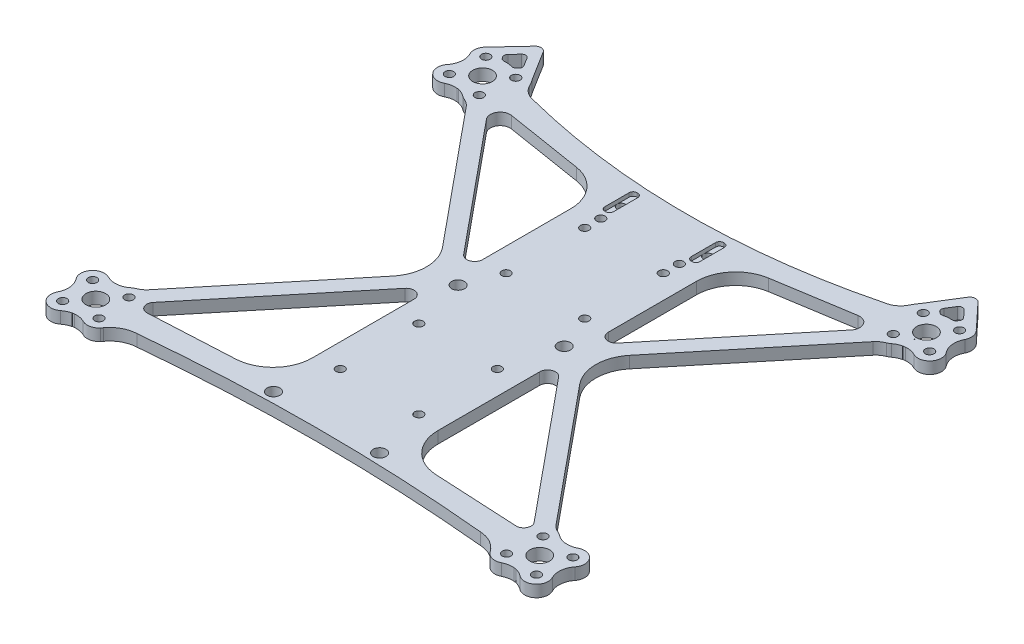
SolidWorks part; units mm, degrees
ref_plane "Front Plane" through (0, 0, 0) normal (0, 0, 1) x (1, 0, 0)
ref_plane "Top Plane" through (0, 0, 0) normal (0, 1, 0) x (1, 0, 0)
ref_plane "Right Plane" through (0, 0, 0) normal (1, 0, 0) x (0, 0, -1)
sketch "Sketch1" plane through (0, 0, 0) normal (0, 1, 0) x (1, 0, 0)
  line L0 (0, 42.225) -> (0, -42.225) construction
  line L1 (16, 42.225) -> (-16, 42.225)
  line L2 (16, 42.225) -> (16, -42.225)
  line L3 (16, -42.225) -> (-16, -42.225)
  line L4 (-16, 42.225) -> (-16, -42.225)
  line L5 (16, 42.225) -> (-16, -42.225) construction
  line L6 (16, -42.225) -> (-16, 42.225) construction
  line L17 (-16, 42.225) -> (16, 42.225)
  line L19 (-16, 42.225) -> (-16, 52.425)
  line L20 (-10, 36) -> (10, 36)
  line L21 (-10, 36) -> (-10, 16)
  line L22 (-10, 16) -> (10, 16)
  line L23 (10, 36) -> (10, 16)
  line L24 (-10, 36) -> (10, 16) construction
  line L25 (-10, 16) -> (10, 36) construction
  line L26 (-14.5, 10.775) -> (14.5, 10.775)
  line L27 (-14.5, 10.775) -> (-14.5, 41.225)
  line L28 (-14.5, 41.225) -> (14.5, 41.225)
  line L29 (14.5, 10.775) -> (14.5, 41.225)
  line L30 (-14.5, 10.775) -> (14.5, 41.225) construction
  line L31 (-14.5, 41.225) -> (14.5, 10.775) construction
  line L32 (-10, -6.225) -> (10, -6.225)
  line L33 (-10, -6.225) -> (-10, -26.225)
  line L34 (-10, -26.225) -> (10, -26.225)
  line L35 (10, -6.225) -> (10, -26.225)
  line L36 (-10, -6.225) -> (10, -26.225) construction
  line L37 (-10, -26.225) -> (10, -6.225) construction
  line L38 (-15.75, -36.225) -> (15.75, -36.225)
  line L39 (-15.75, -36.225) -> (-15.75, 3.775)
  line L40 (-15.75, 3.775) -> (15.75, 3.775)
  line L41 (15.75, -36.225) -> (15.75, 3.775)
  line L42 (-15.75, -36.225) -> (15.75, 3.775) construction
  line L43 (-15.75, 3.775) -> (15.75, -36.225) construction
  line L58 (-16, 52.425) -> (16, 52.425)
  line L63 (-12.1, 50.425) -> (-9.9, 50.425)
  line L64 (-12.1, 50.425) -> (-12.1, 42.225)
  line L65 (-12.1, 42.225) -> (-9.9, 42.225)
  line L66 (-9.9, 50.425) -> (-9.9, 42.225)
  line L67 (-12.1, 50.425) -> (-9.9, 42.225) construction
  line L68 (-12.1, 42.225) -> (-9.9, 50.425) construction
  line L78 (12.1, 50.425) -> (9.9, 50.425)
  line L79 (12.1, 50.425) -> (12.1, 42.225)
  line L80 (12.1, 42.225) -> (9.9, 42.225)
  line L81 (9.9, 50.425) -> (9.9, 42.225)
  line L82 (-14.5, 10.775) -> (-14.5, 3.775) construction
  line L83 (-14.5, 7.275) -> (16, 7.275) construction
  line L89 (-13.5, -37.225) -> (-16, -37.225) construction
  line L90 (16, 42.225) -> (16, 52.425)
  circle A3 centre (-10, 36) radius 1.1
  circle A4 centre (10, 36) radius 1.1
  circle A5 centre (10, 16) radius 1.1
  circle A6 centre (-10, 16) radius 1.1
  circle A7 centre (-10, -6.225) radius 1.1
  circle A8 centre (10, -6.225) radius 1.1
  circle A9 centre (10, -26.225) radius 1.1
  circle A10 centre (-10, -26.225) radius 1.1
  circle A37 centre (-13.5, 7.275) radius 2.5
  circle A38 centre (-13.5, 7.275) radius 1.625
  circle A39 centre (13.5, 7.275) radius 1.625
  circle A40 centre (-13.5, -39.725) radius 2.5
  circle A41 centre (-13.5, -39.725) radius 1.625
  circle A42 centre (13.5, -39.725) radius 1.625
  circle A43 centre (-11, 46.325) radius 1.1
  circle A44 centre (11, 46.325) radius 1.1
  point P0 (0, 0)
  point P8 (0, 0)
  point P16 (0, 26)
  point P26 (0, 26)
  point P31 (0, -16.225)
  point P36 (0, -16.225)
  point P61 (-11, 46.325)
  dimension "D3" = 22
  dimension "D4" = 2
  dimension "D17" = 2.2
  dimension "D22" = 5
  dimension "D23" = 3.25
  dimension "D8" = 32
  dimension "D10" = 20
  dimension "D11" = 29
  dimension "D12" = 30.45
  dimension "D13" = 40
  dimension "D14" = 31.5
  dimension "D15" = 1
  dimension "D16" = 7
  dimension "D18" = 2.2
  dimension "D20" = 8.2
  dimension "D24" = 1
extrude "Base shape" add sketch "Sketch1" along normal blind 2 contours L1 L90 L58 L19 L17 L64 L63 L66 L81 L78 L79 | A43 L64 L17 L66 | A43 L66 L63 L64 | L81 A44 L79 L78 | L79 A44 L81 L17 | L4 L3 L2 L1 | A3 | A4 | A6 | A5 | A39 | A38 | A7 | A8 | A9 | A10 | A41 | A42 region at (0, 0, -47.4493) region at (11, 0, -43.8523) region at (11, 0, -48.7977) region at (-11, 0, -43.8523) region at (-11, 0, -48.7977)
sketch "Sketch2" plane through (0, 2, 0) normal (0, -1, 0) x (1, 0, 0)
  line L0 (0, -52.425) -> (0, 42.225) construction
  line L1 (11.1, -42.225) -> (10.9, -42.225)
  line L2 (12.1, -43.225) -> (12.1, -49.425)
  line L3 (11.1, -50.425) -> (10.9, -50.425)
  line L4 (9.9, -43.225) -> (9.9, -49.425)
  line L5 (12.1, -42.225) -> (9.9, -50.425) construction
  line L6 (12.1, -50.425) -> (9.9, -42.225) construction
  line L12 (16, 42.225) -> (-16, 42.225) construction
  line L13 (-11.1, -42.225) -> (-10.9, -42.225)
  line L14 (-12.1, -43.225) -> (-12.1, -49.425)
  line L15 (-11.1, -50.425) -> (-10.9, -50.425)
  line L20 (-9.9, -43.225) -> (-9.9, -49.425)
  line L21 (-16, -52.425) -> (16, -52.425) construction
  arc A2 (12.1, -49.425) -> (11.1, -50.425) centre (11.1, -49.425) cw
  arc A3 (10.9, -50.425) -> (9.9, -49.425) centre (10.9, -49.425) cw
  arc A4 (10.9, -42.225) -> (9.9, -43.225) centre (10.9, -43.225) ccw
  arc A5 (11.1, -42.225) -> (12.1, -43.225) centre (11.1, -43.225) cw
  arc A6 (-10.9, -42.225) -> (-9.9, -43.225) centre (-10.9, -43.225) cw
  arc A7 (-11.1, -42.225) -> (-12.1, -43.225) centre (-11.1, -43.225) ccw
  arc A8 (-12.1, -49.425) -> (-11.1, -50.425) centre (-11.1, -49.425) ccw
  arc A9 (-10.9, -50.425) -> (-9.9, -49.425) centre (-10.9, -49.425) ccw
  point P0 (11, -46.325)
  dimension "D3" = 1
  dimension "D1" = 8.2
  dimension "D2" = 2.2
extrude "Cut-Extrude2" cut sketch "Sketch2" along normal blind 1
sketch "Sketch3" plane through (0, 2, 0) normal (0, 1, 0) x (1, 0, 0)
  line L0 (-11.1, 50.425) -> (-10.9, 50.425) construction
  line L1 (-9.9, 49.425) -> (-9.9, 43.225) construction
  line L2 (-10.9, 42.225) -> (-11.1, 42.225) construction
  line L3 (-12.1, 43.225) -> (-12.1, 49.425) construction
  line L4 (-11.1, 50.425) -> (-10.9, 50.425)
  line L5 (-9.9, 49.425) -> (-9.9, 43.225)
  line L6 (-10.9, 42.225) -> (-11.1, 42.225)
  line L7 (-12.1, 43.225) -> (-12.1, 49.425)
  line L8 (-16, 52.425) -> (-16, -42.225)
  line L9 (-16, 52.425) -> (-16, -42.225)
  line L10 (-16, -42.225) -> (16, -42.225)
  line L11 (16, -42.225) -> (16, 52.425)
  line L12 (10.9, 50.425) -> (11.1, 50.425) construction
  line L13 (12.1, 49.425) -> (12.1, 43.225) construction
  line L14 (11.1, 42.225) -> (10.9, 42.225) construction
  line L15 (9.9, 43.225) -> (9.9, 49.425) construction
  line L18 (-16, -42.225) -> (16, -42.225)
  line L24 (10.9, 50.425) -> (11.1, 50.425)
  line L25 (12.1, 49.425) -> (12.1, 43.225)
  line L30 (11.1, 42.225) -> (10.9, 42.225)
  line L31 (9.9, 43.225) -> (9.9, 49.425)
  line L36 (16, -42.225) -> (16, 52.425)
  line L37 (16, 52.425) -> (-16, 52.425)
  line L38 (16, 52.425) -> (-16, 52.425)
  circle A0 centre (13.5, -39.725) radius 1.625 construction
  circle A1 centre (-13.5, -39.725) radius 1.625 construction
  circle A2 centre (-13.5, 7.275) radius 1.625 construction
  circle A3 centre (-10, -6.225) radius 1.1 construction
  circle A4 centre (-10, -26.225) radius 1.1 construction
  circle A5 centre (10, -26.225) radius 1.1 construction
  circle A6 centre (10, -6.225) radius 1.1 construction
  circle A7 centre (13.5, 7.275) radius 1.625 construction
  arc A13 (-11.1, 50.425) -> (-12.1, 49.425) centre (-11.1, 49.425) ccw construction
  arc A14 (-9.9, 49.425) -> (-10.9, 50.425) centre (-10.9, 49.425) ccw construction
  circle A24 centre (-10, 16) radius 1.1 construction
  circle A25 centre (-10, 36) radius 1.1 construction
  circle A26 centre (10, 36) radius 1.1 construction
  circle A27 centre (10, 16) radius 1.1 construction
  circle A28 centre (10, 16) radius 1.1
  circle A29 centre (10, 36) radius 1.1
  circle A30 centre (-10, 36) radius 1.1
  circle A31 centre (-10, 16) radius 1.1
  circle A32 centre (13.5, 7.275) radius 1.625
  circle A33 centre (10, -6.225) radius 1.1
  circle A34 centre (10, -26.225) radius 1.1
  circle A35 centre (-10, -26.225) radius 1.1
  circle A36 centre (-10, -6.225) radius 1.1
  circle A37 centre (13.5, -39.725) radius 1.625
  circle A38 centre (-13.5, -39.725) radius 1.625
  circle A39 centre (-13.5, 7.275) radius 1.625
  arc A40 (-10.9, 42.225) -> (-9.9, 43.225) centre (-10.9, 43.225) ccw construction
  arc A41 (-12.1, 43.225) -> (-11.1, 42.225) centre (-11.1, 43.225) ccw construction
  arc A42 (-11.1, 50.425) -> (-12.1, 49.425) centre (-11.1, 49.425) ccw
  arc A43 (-9.9, 49.425) -> (-10.9, 50.425) centre (-10.9, 49.425) ccw
  arc A44 (-10.9, 42.225) -> (-9.9, 43.225) centre (-10.9, 43.225) ccw
  arc A45 (-12.1, 43.225) -> (-11.1, 42.225) centre (-11.1, 43.225) ccw
  arc A46 (10.9, 50.425) -> (9.9, 49.425) centre (10.9, 49.425) ccw construction
  arc A47 (12.1, 49.425) -> (11.1, 50.425) centre (11.1, 49.425) ccw construction
  arc A48 (11.1, 42.225) -> (12.1, 43.225) centre (11.1, 43.225) ccw construction
  arc A49 (9.9, 43.225) -> (10.9, 42.225) centre (10.9, 43.225) ccw construction
  arc A50 (10.9, 50.425) -> (9.9, 49.425) centre (10.9, 49.425) ccw
  arc A51 (12.1, 49.425) -> (11.1, 50.425) centre (11.1, 49.425) ccw
  arc A52 (11.1, 42.225) -> (12.1, 43.225) centre (11.1, 43.225) ccw
  arc A53 (9.9, 43.225) -> (10.9, 42.225) centre (10.9, 43.225) ccw
  dimension "D1" = 0
extrude "Thicker base" add sketch "Sketch3" along normal blind 1
sketch "Sketch8" plane through (0, 1, 0) normal (0, 1, 0) x (1, 0, 0)
  line L0 (9.9, 46.325) -> (9.9, 43.225) construction
  line L1 (10.9, 42.225) -> (11.1, 42.225) construction
  line L2 (12.1, 43.225) -> (12.1, 46.325) construction
  line L3 (12.1, 46.325) -> (12.1, 49.425) construction
  line L4 (11.1, 50.425) -> (10.9, 50.425) construction
  line L5 (9.9, 49.425) -> (9.9, 46.325) construction
  line L6 (-12.1, 46.325) -> (-12.1, 43.225) construction
  line L7 (-11.1, 42.225) -> (-10.9, 42.225) construction
  line L8 (-9.9, 43.225) -> (-9.9, 46.325) construction
  line L9 (-9.9, 46.325) -> (-9.9, 49.425) construction
  line L10 (-10.9, 50.425) -> (-11.1, 50.425) construction
  line L11 (-12.1, 49.425) -> (-12.1, 46.325) construction
  line L12 (9.9, 46.325) -> (9.9, 43.225)
  line L13 (10.9, 42.225) -> (11.1, 42.225)
  line L14 (12.1, 43.225) -> (12.1, 46.325)
  line L15 (12.1, 46.325) -> (12.1, 49.425)
  line L16 (11.1, 50.425) -> (10.9, 50.425)
  line L17 (9.9, 49.425) -> (9.9, 46.325)
  line L18 (-12.1, 46.325) -> (-12.1, 43.225)
  line L19 (-11.1, 42.225) -> (-10.9, 42.225)
  line L20 (-9.9, 43.225) -> (-9.9, 46.325)
  line L21 (-9.9, 46.325) -> (-9.9, 49.425)
  line L22 (-10.9, 50.425) -> (-11.1, 50.425)
  line L23 (-12.1, 49.425) -> (-12.1, 46.325)
  arc A0 (9.9, 46.325) -> (12.1, 46.325) centre (11, 46.325) ccw construction
  arc A1 (9.9, 43.225) -> (10.9, 42.225) centre (10.9, 43.225) ccw construction
  arc A2 (11.1, 42.225) -> (12.1, 43.225) centre (11.1, 43.225) ccw construction
  arc A3 (12.1, 46.325) -> (9.9, 46.325) centre (11, 46.325) ccw construction
  arc A4 (12.1, 49.425) -> (11.1, 50.425) centre (11.1, 49.425) ccw construction
  arc A5 (10.9, 50.425) -> (9.9, 49.425) centre (10.9, 49.425) ccw construction
  arc A6 (-12.1, 43.225) -> (-11.1, 42.225) centre (-11.1, 43.225) ccw construction
  arc A7 (-10.9, 42.225) -> (-9.9, 43.225) centre (-10.9, 43.225) ccw construction
  arc A8 (-12.1, 46.325) -> (-9.9, 46.325) centre (-11, 46.325) ccw construction
  arc A9 (-9.9, 49.425) -> (-10.9, 50.425) centre (-10.9, 49.425) ccw construction
  arc A10 (-11.1, 50.425) -> (-12.1, 49.425) centre (-11.1, 49.425) ccw construction
  arc A11 (-9.9, 46.325) -> (-12.1, 46.325) centre (-11, 46.325) ccw construction
  arc A12 (9.9, 46.325) -> (12.1, 46.325) centre (11, 46.325) ccw
  arc A13 (9.9, 43.225) -> (10.9, 42.225) centre (10.9, 43.225) ccw
  arc A14 (11.1, 42.225) -> (12.1, 43.225) centre (11.1, 43.225) ccw
  arc A15 (12.1, 46.325) -> (9.9, 46.325) centre (11, 46.325) ccw
  arc A16 (12.1, 49.425) -> (11.1, 50.425) centre (11.1, 49.425) ccw
  arc A17 (10.9, 50.425) -> (9.9, 49.425) centre (10.9, 49.425) ccw
  arc A18 (-12.1, 43.225) -> (-11.1, 42.225) centre (-11.1, 43.225) ccw
  arc A19 (-10.9, 42.225) -> (-9.9, 43.225) centre (-10.9, 43.225) ccw
  arc A20 (-12.1, 46.325) -> (-9.9, 46.325) centre (-11, 46.325) ccw
  arc A21 (-9.9, 49.425) -> (-10.9, 50.425) centre (-10.9, 49.425) ccw
  arc A22 (-11.1, 50.425) -> (-12.1, 49.425) centre (-11.1, 49.425) ccw
  arc A23 (-9.9, 46.325) -> (-12.1, 46.325) centre (-11, 46.325) ccw
  line M1 (-9.9, 46.325) -> (-9.9, 49.425)
  arc M2 (-9.9, 49.425) -> (-10.9, 50.425) centre (-10.9, 49.425) ccw
  line M3 (-10.9, 50.425) -> (-11.1, 50.425)
  arc M4 (-11.1, 50.425) -> (-12.1, 49.425) centre (-11.1, 49.425) ccw
  line M5 (-12.1, 49.425) -> (-12.1, 46.325)
  arc M6 (-12.1, 46.325) -> (-9.9, 46.325) centre (-11, 46.325) cw
extrude "Thicker camera mount pocket" add sketch "Sketch8" along normal offset from surface (1 mm away) 1 contours A20 L18 A18 L19 A19 L20 | M6 M1 M2 M3 M4 M5 | L16 A17 L17 A15 L15 A16 | L13 A14 L14 A12 L12 A13 region at (11, 1, -43.9424) region at (11, 1, -48.7076) region at (-11, 1, -43.9424) region at (-11, 1, -48.7076) up to face at (-13.5, 3, 41.35)
sketch "Sketch4" plane through (0, 0, 0) normal (0, -1, 0) x (1, 0, 0)
  line L0 (0, 13.9568) -> (0, -8.6953) construction
  line L1 (-13.1, -38.5) -> (-6.9, -38.5)
  line L2 (-14.1, -39.5) -> (-14.1, -40.7)
  line L3 (-13.1, -41.7) -> (-6.9, -41.7)
  line L4 (-5.9, -39.5) -> (-5.9, -40.7)
  line L5 (-10, -38.5) -> (-10, -41.7) construction
  line L7 (13.1, -38.5) -> (6.9, -38.5)
  line L8 (14.1, -39.5) -> (14.1, -40.7)
  line L9 (13.1, -41.7) -> (6.9, -41.7)
  line L10 (5.9, -39.5) -> (5.9, -40.7)
  line L12 (-14.1, -40.1) -> (-5.9, -40.1) construction
  circle A0 centre (-10, -36) radius 2
  arc A9 (14.1, -40.7) -> (13.1, -41.7) centre (13.1, -40.7) cw
  arc A10 (13.1, -38.5) -> (14.1, -39.5) centre (13.1, -39.5) cw
  arc A11 (6.9, -41.7) -> (5.9, -40.7) centre (6.9, -40.7) cw
  arc A12 (6.9, -38.5) -> (5.9, -39.5) centre (6.9, -39.5) ccw
  arc A13 (-6.9, -41.7) -> (-5.9, -40.7) centre (-6.9, -40.7) ccw
  arc A14 (-6.9, -38.5) -> (-5.9, -39.5) centre (-6.9, -39.5) cw
  arc A15 (-14.1, -40.7) -> (-13.1, -41.7) centre (-13.1, -40.7) ccw
  arc A16 (-13.1, -38.5) -> (-14.1, -39.5) centre (-13.1, -39.5) ccw
  point P9 (-10, -38)
  point P19 (14.1, -41.7)
  point P24 (14.1, -38.5)
  point P27 (5.9, -41.7)
  point P30 (5.9, -38.5)
  point P33 (-5.9, -41.7)
  point P36 (-5.9, -38.5)
  point P39 (-14.1, -41.7)
  point P42 (-14.1, -38.5)
  dimension "D5" = 4
  dimension "D6" = 1
  dimension "D1" = 8.2
  dimension "D2" = 3.2
  dimension "D3" = 10
  dimension "D4" = 0.5
extrude "Battery holder pockets" cut sketch "Sketch4" against normal blind 1 contours L4 L1 L2 L3 | L7 L10 L9 L8 region at (-10, 0, -40.1) region at (10, 0, -40.1)
sketch "Sketch5" plane through (0, 1, 0) normal (0, -1, 0) x (1, 0, 0)
  line L0 (-10, -38.5) -> (-10, -41.7) construction
  line L2 (-13.1, -41.7) -> (-6.9, -41.7) construction
  line L3 (0, 5.9884) -> (0, -5.6723) construction
  line L4 (-13.1, -38.5) -> (-6.9, -38.5) construction
  circle A0 centre (-10, -40.1) radius 1.1
  circle A1 centre (10, -40.1) radius 1.1
  dimension "D1" = 2.2
extrude "Battery holder holes" cut sketch "Sketch5" against normal up to next
sketch "Sketch6" [suppressed] plane through (0, 0, 0) normal (0, -1, 0) x (1, 0, 0)
  line L0 (0, -5.1) -> (0, 9.653) construction
  line L1 (16, 42.225) -> (16, -52.425) construction
  line L8 (-13.5, -7.275) -> (13.5, -7.275) construction
  line L10 (-16, -25.775) -> (16, -25.775) construction
  line L13 (17.5, -34.275) -> (19, -34.275)
  line L14 (16, -37.275) -> (19, -37.275)
  line L15 (16, -37.275) -> (16, -14.275)
  line L16 (16, -14.275) -> (19, -14.275)
  line L17 (19, -37.275) -> (19, -14.275)
  line L18 (16, -37.275) -> (19, -14.275) construction
  line L19 (16, -14.275) -> (19, -37.275) construction
  line L20 (16, -35.775) -> (17.5, -35.775)
  line L21 (16, -35.775) -> (16, -15.775)
  line L22 (16, -15.775) -> (17.5, -15.775)
  line L23 (17.5, -35.775) -> (17.5, -15.775)
  line L24 (16, -35.775) -> (17.5, -15.775) construction
  line L25 (16, -15.775) -> (17.5, -35.775) construction
  line L26 (17.5, -17.275) -> (19, -17.275)
  line L27 (-17.5, -34.275) -> (-19, -34.275)
  line L28 (-17.5, -17.275) -> (-19, -17.275)
  line L29 (-16, -35.775) -> (-16, -15.775)
  line L30 (-16, -35.775) -> (-17.5, -35.775)
  line L31 (-17.5, -35.775) -> (-17.5, -15.775)
  line L32 (-16, -15.775) -> (-17.5, -15.775)
  line L33 (-16, -37.275) -> (-16, -14.275)
  line L34 (-16, -37.275) -> (-19, -37.275)
  line L35 (-19, -37.275) -> (-19, -14.275)
  line L36 (-16, -14.275) -> (-19, -14.275)
  line L37 (16, 22.725) -> (19, 22.725)
  line L38 (16, 22.725) -> (16, -0.275)
  line L39 (16, -0.275) -> (19, -0.275)
  line L40 (19, 22.725) -> (19, -0.275)
  line L41 (16, 21.225) -> (17.5, 21.225)
  line L42 (16, 21.225) -> (16, 1.225)
  line L43 (16, 1.225) -> (17.5, 1.225)
  line L44 (17.5, 21.225) -> (17.5, 1.225)
  line L45 (17.5, 2.725) -> (19, 2.725)
  line L46 (17.5, 19.725) -> (19, 19.725)
  line L47 (-17.5, 19.725) -> (-19, 19.725)
  line L48 (-17.5, 2.725) -> (-19, 2.725)
  line L49 (-16, 21.225) -> (-16, 1.225)
  line L50 (-16, 21.225) -> (-17.5, 21.225)
  line L51 (-17.5, 21.225) -> (-17.5, 1.225)
  line L52 (-16, 1.225) -> (-17.5, 1.225)
  line L53 (-16, 22.725) -> (-16, -0.275)
  line L54 (-16, 22.725) -> (-19, 22.725)
  line L55 (-19, 22.725) -> (-19, -0.275)
  line L56 (-16, -0.275) -> (-19, -0.275)
  point P19 (17.5, -25.775)
  point P25 (16.75, -25.775)
  dimension "D1" = 14
  dimension "D4" = 23
  dimension "D5" = 3
  dimension "D6" = 1.5
  dimension "D7" = 20
  dimension "D8" = 1.5
extrude "Strap holders" [suppressed] add sketch "Sketch6" against normal up to surface (2 mm away) up to face at (-11, 2, -43.6726)
fillet "Strap holder fillets" [suppressed] radius 0.75
fillet "Edge fillets" [suppressed] radius 2.5
sketch "Sketch7" plane through (0, 3, 0) normal (0, 1, 0) x (1, 0, 0)
  line L0 (-56.5, 56.5) -> (-16, 50.0116) construction
  line L1 (56.5, -56.5) -> (-56.5, -56.5)
  line L2 (56.5, -56.5) -> (56.5, 56.5)
  line L3 (56.5, 56.5) -> (-56.5, 56.5)
  line L4 (-56.5, -56.5) -> (-56.5, 56.5)
  line L5 (56.5, -56.5) -> (-56.5, 56.5) construction
  line L6 (56.5, 56.5) -> (-56.5, -56.5) construction
  line L8 (-56.9746, 53.5378) -> (-16.4746, 47.0493)
  line L9 (-47.647, 58.1199) -> (-12.1, 52.425)
  line L10 (-56.0254, 59.4622) -> (-15.5254, 52.9738) construction
  line L11 (-13.5, 7.275) -> (13.5, 7.275) construction
  line L12 (-63.45, 50.7819) -> (-49.55, 62.2181) construction
  line L13 (-56.5, 56.5) -> (-16, 7.275) construction
  line L14 (-58.0444, 55.2293) -> (-16, 4.1271)
  line L15 (-49.3804, 50.9945) -> (-16, 10.4229)
  line L16 (-16, 4.1271) -> (-16.003, 4.1308)
  line L17 (-56.5, 56.5) -> (-60.3121, 61.1333) construction
  line L18 (-56.5, 65.5) -> (-56.5, 47.5) construction
  line L19 (-60.3121, 61.1333) -> (-51.8667, 60.3121) construction
  line L20 (-56.0894, 60.7227) -> (-55.3151, 68.6852) construction
  line L21 (-56.4116, 69.7087) -> (-62.3842, 63.31)
  line L22 (-54.0419, 69.4782) -> (-49.414, 62.0488)
  line L23 (-55.4603, 67.1922) -> (-58.7341, 63.6848)
  line L24 (-55.4603, 67.1922) -> (-52.9235, 63.1198)
  line L25 (-58.0444, -40.6793) -> (-16, 10.4229)
  line L26 (-49.3804, -36.4445) -> (-16, 4.1271)
  line L27 (-56.5, -41.95) -> (-13.5, -39.725) construction
  line L28 (-47.871, -44.5075) -> (-3.7595, -42.225)
  line L29 (-48.1811, -38.5155) -> (-16, -36.8503)
  line L30 (-56.345, -44.946) -> (-14.5762, -42.7847) construction
  line L31 (-56.5, -41.95) -> (-14.7312, -39.7887) construction
  line L32 (-16, -42.225) -> (16, -42.225) construction
  line L33 (-56.655, -38.954) -> (-14.8862, -36.7927) construction
  line L34 (-16.4746, 47.0493) -> (-16, 46.9733)
  line L35 (-12.1, 49.425) -> (-12.1, 52.425) construction
  line L37 (16, 52.425) -> (-16, 52.425) construction
  line L38 (-16, 52.425) -> (-16, -42.225) construction
  line L39 (-54.9556, 57.7707) -> (-12.9111, 6.6685) construction
  line L40 (-56.5, 56.5) -> (-14.4556, 5.3978) construction
  circle A0 centre (-56.5, 56.5) radius 38.1
  circle A1 centre (-56.5, 56.5) radius 9
  circle A2 centre (-56.5, 56.5) radius 6
  circle A3 centre (-51.8667, 60.3121) radius 1.1
  circle A4 centre (-61.1333, 52.6879) radius 1.1
  circle A5 centre (-60.3121, 61.1333) radius 1.1
  circle A6 centre (-52.6879, 51.8667) radius 1.1
  circle A7 centre (-60.3121, 61.1333) radius 3
  circle A8 centre (-51.8667, 60.3121) radius 3
  circle A9 centre (-61.1333, 52.6879) radius 3
  circle A10 centre (-52.6879, 51.8667) radius 3
  circle A12 centre (-56.5, 56.5) radius 2.5
  circle A13 centre (-55.3151, 68.6852) radius 1.5
  circle A14 centre (-67.313, 57.5515) radius 4.864
  circle A15 centre (-57.5515, 45.687) radius 4.864
  circle A16 centre (-43.9819, 62.4587) radius 4.864
  circle A17 centre (-55.5501, 44.5421) radius 4.864
  circle A18 centre (-44.5093, 49.0089) radius 2.5
  circle A20 centre (-56.5, -41.95) radius 6
  circle A21 centre (-52.6879, -37.3167) radius 1.1
  circle A22 centre (-61.1333, -38.1379) radius 1.1
  circle A23 centre (-60.3121, -46.5833) radius 1.1
  circle A24 centre (-51.8667, -45.7621) radius 1.1
  circle A25 centre (-51.8667, -45.7621) radius 3
  circle A26 centre (-52.6879, -37.3167) radius 3
  circle A27 centre (-56.5, -41.95) radius 2.5
  circle A28 centre (-60.3121, -46.5833) radius 3
  circle A29 centre (-67.313, -43.0015) radius 4.864
  circle A30 centre (-61.1333, -38.1379) radius 3
  circle A31 centre (-57.5515, -31.137) radius 4.864
  circle A32 centre (-55.5501, -29.9921) radius 4.864
  circle A34 centre (-56.5, -41.95) radius 9
  circle A35 centre (-55.4485, -52.763) radius 4.864
  circle A38 centre (-43.36, -51.5674) radius 7.2836
  circle A39 centre (-47.0369, -36.5665) radius 1.8873
  point P0 (0, 0)
  point P12 (-12.1, 53.527)
  point P13 (0, 0)
  point P36 (-52.6879, 51.8667)
  point P54 (-55.4603, 67.1922)
  point P108 (0, 0)
  point P113 (0, 0)
  point P114 (-16, 11.2332)
  point P117 (-16, 7.275)
  point P122 (0, 0)
  point P125 (-20.143, 9.1626)
  point P127 (0, 0)
  point P129 (0, 0)
  point P130 (0, 0)
  point P131 (0, 0)
  point P132 (0, 0)
  point P133 (0, 0)
  point P134 (0, 0)
  point P135 (0, 0)
  point P136 (-48.1815, -38.5144)
  point P137 (-49.3963, -36.4239)
  point P138 (-16, -36.5665)
  point P139 (0, 0)
  line M26 (-16, -42.225) -> (16, -42.225)
  line M134 (16, 52.425) -> (-16, 52.425)
  line M135 (-16, 52.425) -> (-16, -42.225)
  dimension "D3" = 76.2
  dimension "D4" = 12
  dimension "D5" = 3
  dimension "D10" = 2.2
  dimension "D11" = 5
  dimension "D12" = 3
  dimension "D16" = 5
  dimension "D1" = 113
  dimension "D13" = 8
  dimension "D6" = 3
  dimension "D7" = 3
  dimension "D8" = 2
  dimension "D9" = 2
  dimension "D14" = 3
  dimension "D15" = 3
extrude "Arms" add sketch "Sketch7" against normal up to surface (3 mm away) contours A0 L8 L34 L9 M135 M134 | A1 L8 A0 L9 L3 | A1 L3 L9 | A12 L3 A2 A8 A7 A9 L4 L14 | A12 L4 L8 A10 A2 L3 | A10 L14 L4 A2 | A10 L8 L4 L14 | A12 L14 L8 L4 | A10 L8 A1 L3 A2 | A10 A1 L8 | A18 L8 A1 L15 | A8 A2 L3 A1 | A16 A1 L9 | A8 A1 L24 | A13 L24 A1 L22 | A13 | A13 L21 A1 L23 | A7 L23 A1 | A14 A2 A7 | A14 A9 A2 | A15 A2 A9 | A15 A10 A2 L4 | A1 L14 A0 L15 | A10 L14 A1 | A17 A1 L14 A10 | A17 L14 A1 | A0 L14 L25 L15 | L25 L14 M135 | L25 A34 L26 L14 | A34 L25 A26 | A34 A26 A20 A25 | A39 L26 A34 | A34 A32 A26 L25 | A32 A34 L25 | A26 A31 L4 A20 | L25 A26 A20 L4 | A20 A30 A28 L4 A27 L25 | L4 A27 A20 A25 A26 L25 | L25 A27 L4 | A20 A31 A30 | A20 A30 A29 | A20 A29 A28 | A35 L4 A20 A28 | A35 A25 A20 | A39 A34 L29 | L29 A34 L28 M26 M135 | A38 L28 A34 | A8 | A3 | A7 | A5 | A9 | A4 | A10 | A6 | A26 | A21 | A30 | A22 | A28 | A23 | A25 | A24 region at (-47.184, 3, 45.066) region at (-31.4436, 3, 40.7044) region at (-32.8289, 3, -52.5874) region at (-44.211, 3, -57.0386) region at (-17.2942, 3, -50.2467) region at (-49.0289, 3, 41.2235) region at (-49.1236, 3, -54.6581) region at (-48.8324, 3, -58.0351) region at (-47.1282, 3, -58.5028) region at (-24.8075, 3, -17.9625) region at (-41.5668, 3, -38.3497) region at (-57.4052, 3, 48.163) region at (-54.4445, 3, 47.8724) region at (-52.9638, 3, -55.2655) region at (-52.25, 3, -56.6697) region at (-49.418, 3, -51.52) region at (-47.4889, 3, -50.715) region at (-52.3363, 3, -48.2332) region at (-16.8633, 3, -7.275) region at (-34.0657, 3, 14.6748) region at (-62.4224, 3, 44.0055) region at (-57.252, 3, 47.2609) region at (-53.8793, 3, 42.8642) region at (-48.0098, 3, 38.2823) region at (-52.9788, 3, -65.9755) region at (-52.3363, 3, 33.6832) region at (-52.9015, 3, -48.7171) region at (-52.1414, 3, -48.8113) region at (-49.026, 3, 36.4293) region at (-56.6984, 3, -53.811) region at (-55.8748, 3, -53.0321) region at (-55.3151, 3, -68.6852) region at (-52.4447, 3, -63.9477) region at (-52.1414, 3, 34.2613) region at (-52.9015, 3, 34.1671) region at (-58.5555, 3, 36.0276) region at (-58.5555, 3, -50.5776) region at (-62.7075, 3, 41.0741) region at (-56.0913, 3, -51.6584) region at (-58.1296, 3, -66.4764) region at (-55.5948, 3, 35.737) region at (-55.5948, 3, -50.287) region at (-62.7075, 3, -55.6241) region at (-56.6933, 3, 39.2492) region at (-59.0444, 3, -64.5895) region at (-56.0913, 3, 37.1084) region at (-62.4224, 3, -58.5555) up to face at (-13.5, 0, 41.35)
fillet "Motor protector fillets" radius 1 5 edges at (-52.9235, 1.5, -63.1198) (-54.2913, 1.5, -62.0787) (-57.5925, 1.5, -62.3997) (-58.7341, 1.5, -63.6848) (-55.4603, 1.5, -67.1922)
mirror "Arms mirror" about plane through (0, 0, 0) normal (1, 0, 0) of "Arms", "Motor protector fillets"
fillet "Arm fillets outer" radius 10 6 edges at (18.5899, 1.5, -7.275) (-16, 1.5, -46.9733) (16, 1.5, -46.9733) (16, 1.5, 36.8503) (-16, 1.5, 36.8503) (-18.5899, 1.5, -7.275)
fillet "Arm fillets inner" radius 2 4 edges at (16, 1.5, -10.4229) (16, 1.5, -4.1271) (-16, 1.5, -4.1271) (-16, 1.5, -10.4229)
sketch "Sketch9" plane through (0, 0, 0) normal (0, -1, 0) x (1, 0, 0)
  line L0 (0, 56.7966) -> (0, -145.2298) construction
  line L21 (-12.1, -52.425) -> (12.1, -52.425)
  line L22 (12.1, -52.425) -> (44.7513, -57.656)
  line L23 (49.414, -62.0488) -> (54.0419, -69.4782)
  line L24 (56.4116, -69.7087) -> (62.3842, -63.31)
  line L25 (56.5, -50.5) -> (56.5, -50.436)
  line L26 (51.7941, -47.6324) -> (23.8173, -13.6285)
  line L27 (23.8173, -0.9215) -> (51.7941, 33.0824)
  line L28 (56.5, 35.886) -> (56.5, 35.95)
  line L29 (56.5, 48.014) -> (56.5, 47.95)
  line L30 (43.7364, 44.2936) -> (3.7595, 42.225)
  line L31 (3.7595, 42.225) -> (-3.7595, 42.225)
  line L32 (-3.7595, 42.225) -> (-43.7364, 44.2936)
  line L33 (-56.5, 47.95) -> (-56.5, 48.014)
  line L34 (-56.5, 35.95) -> (-56.5, 35.886)
  line L35 (-51.7941, 33.0824) -> (-23.8173, -0.9215)
  line L36 (-23.8173, -13.6285) -> (-51.7941, -47.6324)
  line L37 (-56.5, -50.436) -> (-56.5, -50.5)
  line L38 (-62.3842, -63.31) -> (-56.4116, -69.7087)
  line L39 (-54.0419, -69.4782) -> (-49.414, -62.0488)
  line L40 (-44.7513, -57.656) -> (-12.1, -52.425)
  line L41 (-12.1, -52.425) -> (12.1, -52.425)
  line L42 (12.1, -52.425) -> (44.7513, -57.656)
  line L43 (49.414, -62.0488) -> (54.0419, -69.4782)
  line L44 (56.4116, -69.7087) -> (62.3842, -63.31)
  line L45 (56.5, -50.5) -> (56.5, -50.436)
  line L46 (51.7941, -47.6324) -> (23.8173, -13.6285)
  line L47 (23.8173, -0.9215) -> (51.7941, 33.0824)
  line L48 (56.5, 35.886) -> (56.5, 35.95)
  line L49 (56.5, 48.014) -> (56.5, 47.95)
  line L50 (43.7364, 44.2936) -> (3.7595, 42.225)
  line L51 (3.7595, 42.225) -> (-3.7595, 42.225)
  line L52 (-3.7595, 42.225) -> (-43.7364, 44.2936)
  line L53 (-56.5, 47.95) -> (-56.5, 48.014)
  line L54 (-56.5, 35.95) -> (-56.5, 35.886)
  line L55 (-51.7941, 33.0824) -> (-23.8173, -0.9215)
  line L56 (-23.8173, -13.6285) -> (-51.7941, -47.6324)
  line L57 (-56.5, -50.436) -> (-56.5, -50.5)
  line L58 (-62.3842, -63.31) -> (-56.4116, -69.7087)
  line L59 (-54.0419, -69.4782) -> (-49.414, -62.0488)
  line L60 (-44.7513, -57.656) -> (-12.1, -52.425)
  circle A0 centre (0, -232.4697) radius 180.4509
  circle A1 centre (0, 502.2082) radius 459.9986
  arc A55 (48.3737, -60.3682) -> (44.7513, -57.656) centre (43.9819, -62.4587) ccw
  arc A56 (48.3737, -60.3682) -> (49.414, -62.0488) centre (56.5, -56.5) ccw
  arc A57 (54.0419, -69.4782) -> (56.4116, -69.7087) centre (55.3151, -68.6852) ccw
  arc A58 (62.2181, -63.45) -> (62.3842, -63.31) centre (56.5, -56.5) ccw
  arc A59 (62.2181, -63.45) -> (62.9828, -59.7669) centre (60.3121, -61.1333) ccw
  arc A60 (63.4908, -54.5433) -> (62.9828, -59.7669) centre (67.313, -57.5515) ccw
  arc A61 (63.4908, -54.5433) -> (59.7669, -50.0172) centre (61.1333, -52.6879) ccw
  arc A62 (57.0807, -50.5282) -> (59.7669, -50.0172) centre (57.5515, -45.687) ccw
  arc A63 (57.0807, -50.5282) -> (56.5, -50.5) centre (56.5, -56.5) ccw
  arc A64 (54.5433, -49.5092) -> (56.5, -50.436) centre (57.5515, -45.687) ccw
  arc A65 (54.5433, -49.5092) -> (53.7798, -49.0724) centre (52.6879, -51.8667) ccw
  arc A66 (51.7941, -47.6324) -> (53.7798, -49.0724) centre (55.5501, -44.5421) ccw
  arc A67 (23.8173, -0.9215) -> (23.8173, -13.6285) centre (31.5395, -7.275) ccw
  arc A68 (53.7798, 34.5224) -> (51.7941, 33.0824) centre (55.5501, 29.9921) ccw
  arc A69 (53.7798, 34.5224) -> (54.5433, 34.9592) centre (52.6879, 37.3167) ccw
  arc A70 (56.5, 35.886) -> (54.5433, 34.9592) centre (57.5515, 31.137) ccw
  arc A71 (56.5, 35.95) -> (57.0807, 35.9782) centre (56.5, 41.95) ccw
  arc A72 (59.7669, 35.4672) -> (57.0807, 35.9782) centre (57.5515, 31.137) ccw
  arc A73 (59.7669, 35.4672) -> (63.4908, 39.9933) centre (61.1333, 38.1379) ccw
  arc A74 (62.9828, 45.2169) -> (63.4908, 39.9933) centre (67.313, 43.0015) ccw
  arc A75 (62.9828, 45.2169) -> (58.4567, 48.9408) centre (60.3121, 46.5833) ccw
  arc A76 (56.5, 48.014) -> (58.4567, 48.9408) centre (55.4485, 52.763) ccw
  arc A77 (56.5, 47.95) -> (55.9193, 47.9218) centre (56.5, 41.95) ccw
  arc A78 (53.2331, 48.4328) -> (55.9193, 47.9218) centre (55.4485, 52.763) ccw
  arc A79 (53.2331, 48.4328) -> (49.55, 47.6681) centre (51.8667, 45.7621) ccw
  arc A80 (49.55, 47.6681) -> (49.2375, 47.2656) centre (56.5, 41.95) ccw
  arc A81 (43.7364, 44.2936) -> (49.2375, 47.2656) centre (43.36, 51.5674) ccw
  arc A82 (-49.2375, 47.2656) -> (-43.7364, 44.2936) centre (-43.36, 51.5674) ccw
  arc A83 (-49.2375, 47.2656) -> (-49.55, 47.6681) centre (-56.5, 41.95) ccw
  arc A84 (-49.55, 47.6681) -> (-53.2331, 48.4328) centre (-51.8667, 45.7621) ccw
  arc A85 (-55.9193, 47.9218) -> (-53.2331, 48.4328) centre (-55.4485, 52.763) ccw
  arc A86 (-55.9193, 47.9218) -> (-56.5, 47.95) centre (-56.5, 41.95) ccw
  arc A87 (-58.4567, 48.9408) -> (-56.5, 48.014) centre (-55.4485, 52.763) ccw
  arc A88 (-58.4567, 48.9408) -> (-62.9828, 45.2169) centre (-60.3121, 46.5833) ccw
  arc A89 (-63.4908, 39.9933) -> (-62.9828, 45.2169) centre (-67.313, 43.0015) ccw
  arc A90 (-63.4908, 39.9933) -> (-59.7669, 35.4672) centre (-61.1333, 38.1379) ccw
  arc A91 (-57.0807, 35.9782) -> (-59.7669, 35.4672) centre (-57.5515, 31.137) ccw
  arc A92 (-57.0807, 35.9782) -> (-56.5, 35.95) centre (-56.5, 41.95) ccw
  arc A93 (-54.5433, 34.9592) -> (-56.5, 35.886) centre (-57.5515, 31.137) ccw
  arc A94 (-54.5433, 34.9592) -> (-53.7798, 34.5224) centre (-52.6879, 37.3167) ccw
  arc A95 (-51.7941, 33.0824) -> (-53.7798, 34.5224) centre (-55.5501, 29.9921) ccw
  arc A96 (-23.8173, -13.6285) -> (-23.8173, -0.9215) centre (-31.5395, -7.275) ccw
  arc A97 (-53.7798, -49.0724) -> (-51.7941, -47.6324) centre (-55.5501, -44.5421) ccw
  arc A98 (-53.7798, -49.0724) -> (-54.5433, -49.5092) centre (-52.6879, -51.8667) ccw
  arc A99 (-56.5, -50.436) -> (-54.5433, -49.5092) centre (-57.5515, -45.687) ccw
  arc A100 (-56.5, -50.5) -> (-57.0807, -50.5282) centre (-56.5, -56.5) ccw
  arc A101 (-59.7669, -50.0172) -> (-57.0807, -50.5282) centre (-57.5515, -45.687) ccw
  arc A102 (-59.7669, -50.0172) -> (-63.4908, -54.5433) centre (-61.1333, -52.6879) ccw
  arc A103 (-62.9828, -59.7669) -> (-63.4908, -54.5433) centre (-67.313, -57.5515) ccw
  arc A104 (-62.9828, -59.7669) -> (-62.2181, -63.45) centre (-60.3121, -61.1333) ccw
  arc A105 (-62.3842, -63.31) -> (-62.2181, -63.45) centre (-56.5, -56.5) ccw
  arc A106 (-56.4116, -69.7087) -> (-54.0419, -69.4782) centre (-55.3151, -68.6852) ccw
  arc A107 (-49.414, -62.0488) -> (-48.3737, -60.3682) centre (-56.5, -56.5) ccw
  arc A108 (-44.7513, -57.656) -> (-48.3737, -60.3682) centre (-43.9819, -62.4587) ccw
  arc A109 (48.3737, -60.3682) -> (44.7513, -57.656) centre (43.9819, -62.4587) ccw
  arc A110 (48.3737, -60.3682) -> (49.414, -62.0488) centre (56.5, -56.5) ccw
  arc A111 (54.0419, -69.4782) -> (56.4116, -69.7087) centre (55.3151, -68.6852) ccw
  arc A112 (62.2181, -63.45) -> (62.3842, -63.31) centre (56.5, -56.5) ccw
  arc A113 (62.2181, -63.45) -> (62.9828, -59.7669) centre (60.3121, -61.1333) ccw
  arc A114 (63.4908, -54.5433) -> (62.9828, -59.7669) centre (67.313, -57.5515) ccw
  arc A115 (63.4908, -54.5433) -> (59.7669, -50.0172) centre (61.1333, -52.6879) ccw
  arc A116 (57.0807, -50.5282) -> (59.7669, -50.0172) centre (57.5515, -45.687) ccw
  arc A117 (57.0807, -50.5282) -> (56.5, -50.5) centre (56.5, -56.5) ccw
  arc A118 (54.5433, -49.5092) -> (56.5, -50.436) centre (57.5515, -45.687) ccw
  arc A119 (54.5433, -49.5092) -> (53.7798, -49.0724) centre (52.6879, -51.8667) ccw
  arc A120 (51.7941, -47.6324) -> (53.7798, -49.0724) centre (55.5501, -44.5421) ccw
  arc A121 (23.8173, -0.9215) -> (23.8173, -13.6285) centre (31.5395, -7.275) ccw
  arc A122 (53.7798, 34.5224) -> (51.7941, 33.0824) centre (55.5501, 29.9921) ccw
  arc A123 (53.7798, 34.5224) -> (54.5433, 34.9592) centre (52.6879, 37.3167) ccw
  arc A124 (56.5, 35.886) -> (54.5433, 34.9592) centre (57.5515, 31.137) ccw
  arc A125 (56.5, 35.95) -> (57.0807, 35.9782) centre (56.5, 41.95) ccw
  arc A126 (59.7669, 35.4672) -> (57.0807, 35.9782) centre (57.5515, 31.137) ccw
  arc A127 (59.7669, 35.4672) -> (63.4908, 39.9933) centre (61.1333, 38.1379) ccw
  arc A128 (62.9828, 45.2169) -> (63.4908, 39.9933) centre (67.313, 43.0015) ccw
  arc A129 (62.9828, 45.2169) -> (58.4567, 48.9408) centre (60.3121, 46.5833) ccw
  arc A130 (56.5, 48.014) -> (58.4567, 48.9408) centre (55.4485, 52.763) ccw
  arc A131 (56.5, 47.95) -> (55.9193, 47.9218) centre (56.5, 41.95) ccw
  arc A132 (53.2331, 48.4328) -> (55.9193, 47.9218) centre (55.4485, 52.763) ccw
  arc A133 (53.2331, 48.4328) -> (49.55, 47.6681) centre (51.8667, 45.7621) ccw
  arc A134 (49.55, 47.6681) -> (49.2375, 47.2656) centre (56.5, 41.95) ccw
  arc A135 (43.7364, 44.2936) -> (49.2375, 47.2656) centre (43.36, 51.5674) ccw
  arc A136 (-49.2375, 47.2656) -> (-43.7364, 44.2936) centre (-43.36, 51.5674) ccw
  arc A137 (-49.2375, 47.2656) -> (-49.55, 47.6681) centre (-56.5, 41.95) ccw
  arc A138 (-49.55, 47.6681) -> (-53.2331, 48.4328) centre (-51.8667, 45.7621) ccw
  arc A139 (-55.9193, 47.9218) -> (-53.2331, 48.4328) centre (-55.4485, 52.763) ccw
  arc A140 (-55.9193, 47.9218) -> (-56.5, 47.95) centre (-56.5, 41.95) ccw
  arc A141 (-58.4567, 48.9408) -> (-56.5, 48.014) centre (-55.4485, 52.763) ccw
  arc A142 (-58.4567, 48.9408) -> (-62.9828, 45.2169) centre (-60.3121, 46.5833) ccw
  arc A143 (-63.4908, 39.9933) -> (-62.9828, 45.2169) centre (-67.313, 43.0015) ccw
  arc A144 (-63.4908, 39.9933) -> (-59.7669, 35.4672) centre (-61.1333, 38.1379) ccw
  arc A145 (-57.0807, 35.9782) -> (-59.7669, 35.4672) centre (-57.5515, 31.137) ccw
  arc A146 (-57.0807, 35.9782) -> (-56.5, 35.95) centre (-56.5, 41.95) ccw
  arc A147 (-54.5433, 34.9592) -> (-56.5, 35.886) centre (-57.5515, 31.137) ccw
  arc A148 (-54.5433, 34.9592) -> (-53.7798, 34.5224) centre (-52.6879, 37.3167) ccw
  arc A149 (-51.7941, 33.0824) -> (-53.7798, 34.5224) centre (-55.5501, 29.9921) ccw
  arc A150 (-23.8173, -13.6285) -> (-23.8173, -0.9215) centre (-31.5395, -7.275) ccw
  arc A151 (-53.7798, -49.0724) -> (-51.7941, -47.6324) centre (-55.5501, -44.5421) ccw
  arc A152 (-53.7798, -49.0724) -> (-54.5433, -49.5092) centre (-52.6879, -51.8667) ccw
  arc A153 (-56.5, -50.436) -> (-54.5433, -49.5092) centre (-57.5515, -45.687) ccw
  arc A154 (-56.5, -50.5) -> (-57.0807, -50.5282) centre (-56.5, -56.5) ccw
  arc A155 (-59.7669, -50.0172) -> (-57.0807, -50.5282) centre (-57.5515, -45.687) ccw
  arc A156 (-59.7669, -50.0172) -> (-63.4908, -54.5433) centre (-61.1333, -52.6879) ccw
  arc A157 (-62.9828, -59.7669) -> (-63.4908, -54.5433) centre (-67.313, -57.5515) ccw
  arc A158 (-62.9828, -59.7669) -> (-62.2181, -63.45) centre (-60.3121, -61.1333) ccw
  arc A159 (-62.3842, -63.31) -> (-62.2181, -63.45) centre (-56.5, -56.5) ccw
  arc A160 (-56.4116, -69.7087) -> (-54.0419, -69.4782) centre (-55.3151, -68.6852) ccw
  arc A161 (-49.414, -62.0488) -> (-48.3737, -60.3682) centre (-56.5, -56.5) ccw
  arc A162 (-44.7513, -57.656) -> (-48.3737, -60.3682) centre (-43.9819, -62.4587) ccw
  dimension "D1" = 0
extrude "Front radius" cut sketch "Sketch9" against normal up to next contours L60 A0 | L0 A0 L41 | A0 L0 L41 | L42 A0 | L52 A1 | L50 A1 | L51 L0 A1 | L0 L51 A1 region at (1.4098, 0, 42.2189) region at (-1.4098, 0, 42.2189) region at (23.7569, 0, 43.0853) region at (-23.7569, 0, 43.0853) region at (4.5382, 0, -52.2625) region at (-4.5382, 0, -52.2625) region at (28.4737, 0, -54.7407) region at (-28.4737, 0, -54.7407)
